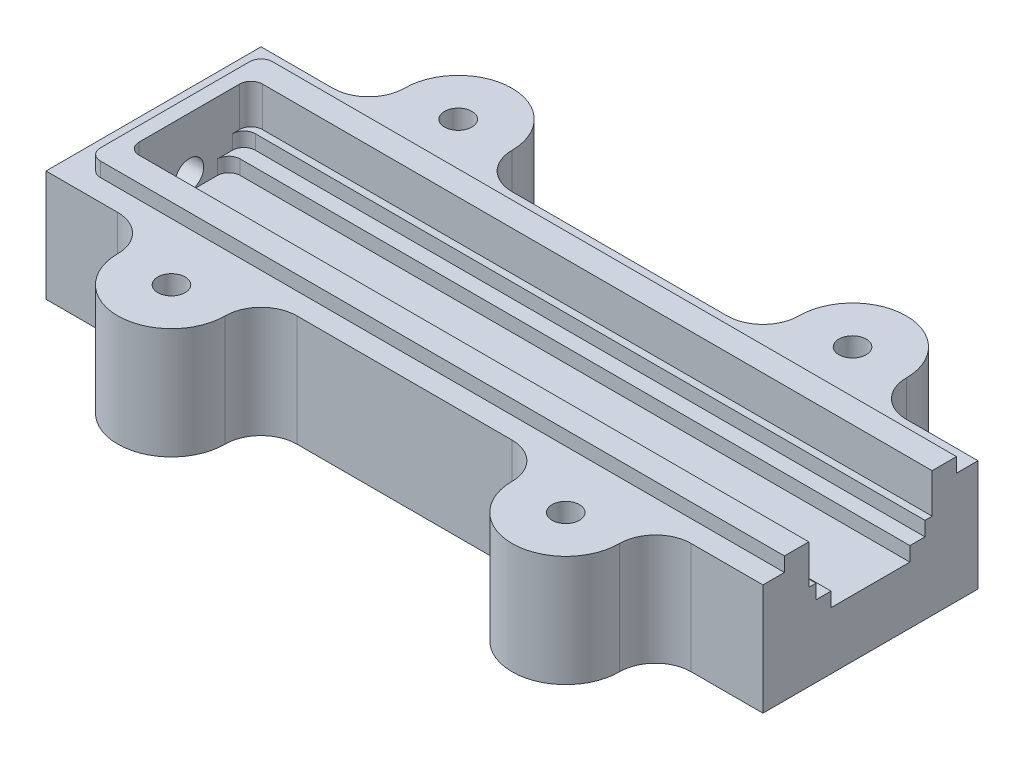
SolidWorks part; units mm, degrees
ref_plane "Front Plane" through (0, 0, 0) normal (0, 0, 1) x (1, 0, 0)
ref_plane "Top Plane" through (0, 0, 0) normal (0, 1, 0) x (1, 0, 0)
ref_plane "Right Plane" through (0, 0, 0) normal (1, 0, 0) x (0, 0, -1)
sketch "Sketch1" plane through (0, 0, 0) normal (0, 1, 0) x (1, 0, 0)
  line L1 (0, 15) -> (100, 15)
  line L2 (0, 15) -> (0, -15)
  line L3 (0, -15) -> (100, -15)
  line L4 (100, 15) -> (100, -15)
  point P4 (0, 0)
  dimension "D1" = 30
  dimension "D2" = 100
extrude "Boss-Extrude1" add sketch "Sketch1" along normal blind 20
sketch "Sketch2" plane through (0, 0, 0) normal (-1, 0, 0) x (0, 0, 1)
  line L0 (-15, 0) -> (15, 0) construction
  line L1 (-7.6, 25.5) -> (7.6, 25.5)
  line L2 (-7.6, 25.5) -> (-7.6, 10)
  line L3 (-7.6, 10) -> (7.6, 10)
  line L4 (7.6, 25.5) -> (7.6, 10)
  point P4 (0, 10)
  dimension "D1" = 15.2
  dimension "D2" = 15.5
  dimension "D3" = 10
extrude "Cut-Extrude1" cut sketch "Sketch2" against normal through all
sketch "Sketch3" plane through (0, 0, 0) normal (-1, 0, 0) x (0, 0, 1)
  line L0 (-7.6, 10) -> (7.6, 10) construction
  line L1 (-5.5, 10) -> (5.5, 10)
  line L2 (-5.5, 10) -> (-5.5, 8)
  line L3 (-5.5, 8) -> (5.5, 8)
  line L4 (5.5, 10) -> (5.5, 8)
  point P6 (0, 8)
  dimension "D1" = 2
  dimension "D2" = 11
extrude "Cut-Extrude2" cut sketch "Sketch3" against normal through all
sketch "Sketch4" plane through (0, 0, 0) normal (-1, 0, 0) x (0, 0, 1)
  line L0 (7.6, 10) -> (7.6, 20) construction
  line L1 (7.6, 12) -> (8.6, 12)
  line L2 (7.6, 12) -> (7.6, 20)
  line L3 (7.6, 20) -> (8.6, 20)
  line L4 (8.6, 12) -> (8.6, 20)
  line L5 (7.6, 20) -> (15, 20) construction
  line L6 (-7.6, 20) -> (-7.6, 10) construction
  line L7 (-7.6, 12) -> (-8.6, 12)
  line L8 (-7.6, 12) -> (-7.6, 20)
  line L9 (-7.6, 20) -> (-8.6, 20)
  line L10 (-8.6, 12) -> (-8.6, 20)
  line L11 (-15, 20) -> (-7.6, 20) construction
  line L12 (5.5, 10) -> (7.6, 10) construction
  point P16 (6.55, 10)
  dimension "D1" = 2
  dimension "D2" = 1
  dimension "D3" = 1
extrude "Cut-Extrude3" cut sketch "Sketch4" against normal through all
sketch "Sketch5" plane through (100, 0, 0) normal (1, 0, 0) x (0, 0, -1)
  line L0 (7.6, 10) -> (5.5, 10) construction
  line L1 (-12, 17.5) -> (12, 17.5)
  line L2 (-15, 17.5) -> (-15, 20)
  line L3 (-15, 20) -> (15, 20)
  line L4 (15, 17.5) -> (15, 20)
  line L5 (-15, 20) -> (-15, 0) construction
  line L6 (15, 20) -> (15, 0) construction
  line L7 (8.6, 20) -> (15, 20) construction
  line L10 (12, 17.5) -> (12, 15.5)
  line L11 (12, 15.5) -> (15, 15.5)
  line L12 (15, 17.5) -> (15, 15.5)
  line L13 (-15, 17.5) -> (-15, 15.5)
  line L14 (-15, 15.5) -> (-12, 15.5)
  line L15 (-12, 17.5) -> (-12, 15.5)
  dimension "D1" = 7.5
  dimension "D2" = 3
  dimension "D3" = 3
  dimension "D4" = 2
  dimension "D5" = 2
extrude "Cut-Extrude4" cut sketch "Sketch5" against normal through all
sketch "Sketch6" plane through (0, 17.5, 0) normal (0, 1, 0) x (1, 0, 0)
  line L0 (0, -8.6) -> (100, -8.6) construction
  line L1 (0, 8.6) -> (5, 8.6)
  line L2 (0, 8.6) -> (0, -8.6)
  line L3 (0, -8.6) -> (5, -8.6)
  line L4 (5, 8.6) -> (5, -8.6)
  dimension "D1" = 5
extrude "Boss-Extrude2" add sketch "Sketch6" against normal up to next
fillet "Fillet1" radius 1.5875 4 edges at (5, 9, 5.5) (5, 14.75, 8.6) (5, 9, -5.5) (5, 14.75, -8.6)
fillet "Fillet2" radius 1.5875 2 edges at (5.1127, 11, 7.6) (5.1127, 11, -7.6)
sketch "Sketch7" plane through (0, 17.5, 0) normal (0, 1, 0) x (1, 0, 0)
  line L0 (0, 12) -> (100, 12) construction
  line L1 (0, -12) -> (3, -12)
  line L2 (0, -12) -> (0, 12)
  line L3 (0, 12) -> (3, 12)
  line L4 (3, -12) -> (3, 12)
  dimension "D1" = 3
extrude "Cut-Extrude5" cut sketch "Sketch7" against normal up to surface (2 mm away) up to face at (50, 15.5, -13.5)
fillet "Fillet3" radius 1.5875 2 edges at (3, 16.5, 12) (3, 16.5, -12)
sketch "Sketch8" plane through (0, 0, 0) normal (0, -1, 0) x (1, 0, 0)
  line L0 (15, 15) -> (15, 20)
  line L1 (0, 15) -> (100, 15) construction
  line L2 (30, 20) -> (30, 15)
  line L3 (30, 15) -> (15, 15)
  line L4 (70, 15) -> (70, 20)
  line L5 (85, 20) -> (85, 15)
  line L6 (85, 15) -> (70, 15)
  line L7 (0, -15) -> (0, 15) construction
  line L8 (100, 15) -> (100, -15) construction
  arc A0 (15, 20) -> (30, 20) centre (22.5, 20) cw
  arc A1 (70, 20) -> (85, 20) centre (77.5, 20) cw
  dimension "D1" = 15
  dimension "D2" = 15
  dimension "D3" = 15
  dimension "D4" = 15
  dimension "D5" = 5
extrude "Boss-Extrude3" add sketch "Sketch8" against normal up to surface (15.5 mm away) up to face at (41.4517, 15.5, 0)
mirror "Mirror1" about plane through (0, 0, 0) normal (0, 0, 1) of "Boss-Extrude3"
sketch "Sketch9" plane through (0, 15.5, 0) normal (0, 1, 0) x (1, 0, 0)
  circle A0 centre (22.5, 20) radius 1.905
  circle A1 centre (77.5, 20) radius 1.905
  circle A2 centre (77.5, -20) radius 1.905
  circle A3 centre (22.5, -20) radius 1.905
  dimension "D1" = 3.81
extrude "Cut-Extrude6" cut sketch "Sketch9" against normal through all
fillet "Fillet4" radius 5 8 edges at (70, 7.75, 15) (85, 7.75, 15) (85, 7.75, -15) (70, 7.75, -15)
sketch "Sketch10" plane through (5, 0, 0) normal (1, 0, 0) x (0, 0, -1)
  line L0 (5.5, 8) -> (-5.5, 8) construction
  circle A0 centre (0, 10) radius 2
  dimension "D1" = 4
extrude "Cut-Extrude7" cut sketch "Sketch10" against normal through all
